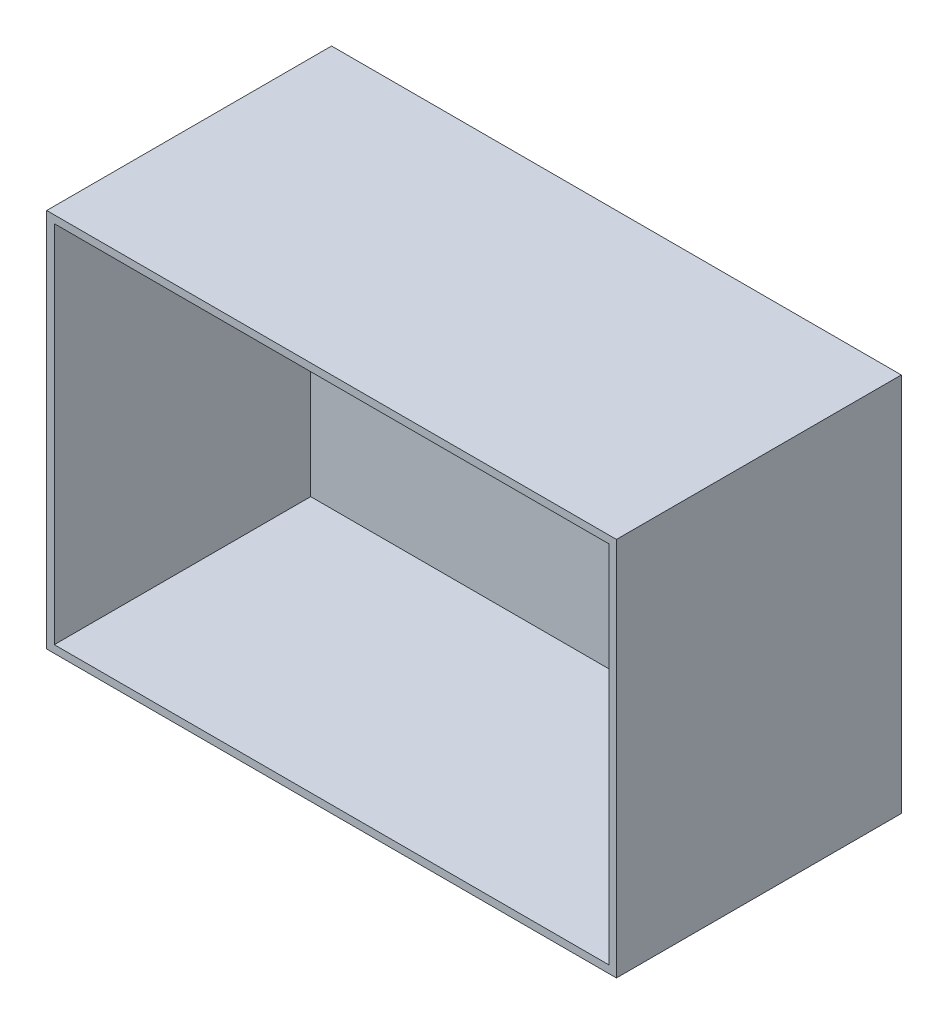
SolidWorks part; units mm, degrees
ref_plane "Plan de face" through (0, 0, 0) normal (0, 0, 1) x (1, 0, 0)
ref_plane "Plan de dessus" through (0, 0, 0) normal (0, 1, 0) x (1, 0, 0)
ref_plane "Plan de droite" through (0, 0, 0) normal (1, 0, 0) x (0, 0, -1)
sketch "Esquisse1" plane through (0, 0, 0) normal (0, 0, 1) x (1, 0, 0)
  line L1 (-39.5872, 21.3052) -> (110.4128, 21.3052)
  line L2 (-39.5872, 21.3052) -> (-39.5872, -78.6948)
  line L3 (-39.5872, -78.6948) -> (110.4128, -78.6948)
  line L4 (110.4128, 21.3052) -> (110.4128, -78.6948)
  dimension "D1" = 150
  dimension "D2" = 100
extrude "Boss.-Extru.2" add sketch "Esquisse1" along normal blind 75 contours L2 L1 L4 L3
sketch "Esquisse4" plane through (0, 0, 75) normal (0, 0, 1) x (1, 0, 0)
  line L0 (-39.5872, 21.3052) -> (110.4128, 21.3052) construction
  line L1 (-37.5872, 19.3052) -> (108.4128, 19.3052)
  line L2 (-37.5872, 19.3052) -> (-37.5872, -76.6948)
  line L3 (-37.5872, -76.6948) -> (108.4128, -76.6948)
  line L4 (108.4128, 19.3052) -> (108.4128, -76.6948)
  line L5 (-39.5872, 21.3052) -> (-39.5872, -78.6948) construction
  dimension "D1" = 146
  dimension "D2" = 96
  dimension "D3" = 2
  dimension "D4" = 2
extrude "Enlèv. mat.-Extru.1" cut sketch "Esquisse4" against normal blind 67.5 contours L2 L1 L4 L3
sketch "Esquisse6" plane through (-37.5872, 0, 0) normal (1, 0, 0) x (0, 0, -1)
  line L0 (-75, 19.3052) -> (-75, -76.6948) construction
  line L1 (-7.5, 19.3052) -> (-75, 19.3052) construction
  point P0 (-75, 8.3052)
  point P1 (-75, 19.3052)
  point P4 (-75, 19.3052)
  point P6 (-70, 19.3052)
  point P7 (-73.0458, 14.4622)
  point P10 (0, 0)
  dimension "D1" = 5
  dimension "D2" = 11
